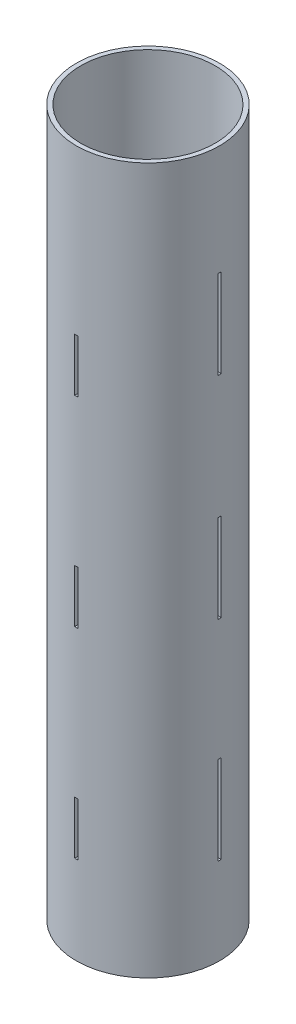
SolidWorks part; units mm, degrees
material "7075-T6 (SN)"
ref_plane "Front Plane" through (0, 0, 0) normal (0, 0, 1) x (1, 0, 0)
ref_plane "Top Plane" through (0, 0, 0) normal (0, 1, 0) x (1, 0, 0)
ref_plane "Right Plane" through (0, 0, 0) normal (1, 0, 0) x (0, 0, -1)
sketch "Sketch1" plane through (0, 0, 0) normal (0, 1, 0) x (1, 0, 0)
  circle A0 centre (0, 0) radius 32.5
  circle A1 centre (0, 0) radius 30.5
  dimension "D1" = 65
  dimension "D2" = 61
extrude "Boss-Extrude1" add sketch "Sketch1" along normal blind 320.25
sketch "Sketch2" plane through (0, 0, 0) normal (1, 0, 0) x (0, 0, -1)
  line L1 (0.75, 270.3798) -> (-0.75, 270.3798)
  line L2 (0.75, 270.3798) -> (0.75, 230.3798)
  line L3 (0.75, 230.3798) -> (-0.75, 230.3798)
  line L4 (-0.75, 270.3798) -> (-0.75, 230.3798)
  line L5 (0.75, 174.5) -> (-0.75, 174.5)
  line L6 (0.75, 174.5) -> (0.75, 134.5)
  line L7 (0.75, 134.5) -> (-0.75, 134.5)
  line L8 (-0.75, 174.5) -> (-0.75, 134.5)
  line L9 (0.75, 79.5) -> (-0.75, 79.5)
  line L10 (0.75, 79.5) -> (0.75, 39.5)
  line L11 (0.75, 39.5) -> (-0.75, 39.5)
  line L12 (-0.75, 79.5) -> (-0.75, 39.5)
extrude "Cut-Extrude1" cut sketch "Sketch2" against normal mid plane 100
sketch "Sketch3" plane through (0, 0, 0) normal (0, 0, 1) x (1, 0, 0)
  line L0 (0, 307.1688) -> (0, 342.7691) construction
  line L1 (-30.4908, 40) -> (-7.7248, 40) construction
  line L2 (-30.4908, 131) -> (-8.527, 131) construction
  line L3 (-30.4908, 221.8798) -> (-7.3578, 221.8798) construction
  line L5 (-0.75, 221.8798) -> (0.75, 221.8798)
  line L6 (-0.75, 221.8798) -> (-0.75, 245.8798)
  line L7 (-0.75, 245.8798) -> (0.75, 245.8798)
  line L8 (0.75, 221.8798) -> (0.75, 245.8798)
  line L9 (-0.75, 131) -> (0.75, 131)
  line L10 (-0.75, 131) -> (-0.75, 155)
  line L11 (-0.75, 155) -> (0.75, 155)
  line L12 (0.75, 131) -> (0.75, 155)
  line L13 (-0.75, 40) -> (0.75, 40)
  line L14 (-0.75, 40) -> (-0.75, 64)
  line L15 (-0.75, 64) -> (0.75, 64)
  line L16 (0.75, 40) -> (0.75, 64)
  dimension "D1" = 0.75
  dimension "D2" = 0.75
  dimension "D3" = 24
  dimension "D4" = 0.75
  dimension "D5" = 0.75
  dimension "D6" = 24
  dimension "D7" = 0.75
  dimension "D8" = 0.75
  dimension "D9" = 24
extrude "Cut-Extrude2" cut sketch "Sketch3" against normal mid plane 100
ref_plane "Plane1" through (0, 0, 0) normal (-0.7071, 0, 0.7071) x (0.7071, 0, 0.7071)
ref_plane "Plane2" through (0, 0, 0) normal (0.7071, 0, 0.7071) x (0.7071, 0, -0.7071)
sketch "Sketch5" plane through (0, 0, 0) normal (-0.7071, 0, 0.7071) x (0.7071, 0, 0.7071)
  line L0 (0, 236.8549) -> (0, 26.8549) construction
  line L1 (9, 236.8549) -> (9, 26.8549)
  line L2 (-9, 236.8549) -> (-9, 26.8549)
  arc A0 (9, 236.8549) -> (-9, 236.8549) centre (0, 236.8549) ccw
  arc A1 (-9, 26.8549) -> (9, 26.8549) centre (0, 26.8549) ccw
  point P3 (0, 131.8549)
extrude "Cut-Extrude3" [suppressed] cut sketch "Sketch5" against normal mid plane 100 contours L1 A1 L2 A0
sketch "Sketch6" plane through (0, 0, 0) normal (0.7071, 0, 0.7071) x (0.7071, 0, -0.7071)
  line L0 (0, 236.8549) -> (0, 26.8549) construction
  line L1 (9, 236.8549) -> (9, 26.8549)
  line L2 (-9, 236.8549) -> (-9, 26.8549)
  arc A0 (9, 236.8549) -> (-9, 236.8549) centre (0, 236.8549) ccw
  arc A1 (-9, 26.8549) -> (9, 26.8549) centre (0, 26.8549) ccw
  point P3 (0, 131.8549)
extrude "Cut-Extrude4" [suppressed] cut sketch "Sketch6" against normal mid plane 100 contours L1 A1 L2 A0
